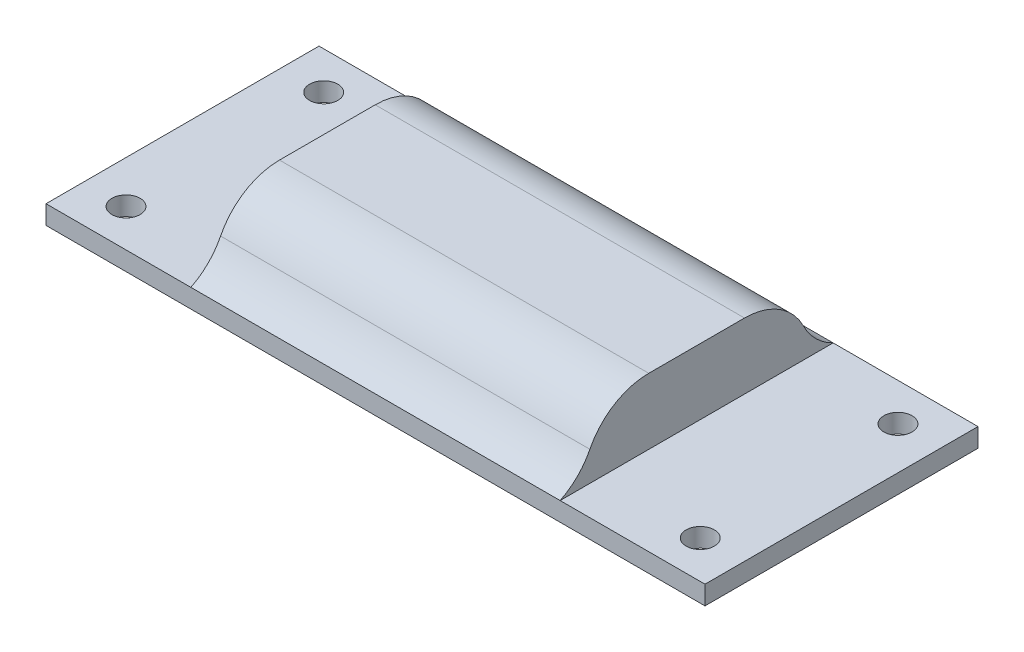
SolidWorks part; units mm, degrees
material "Rubber"
ref_plane "Front Plane" through (0, 0, 0) normal (0, 0, 1) x (1, 0, 0)
ref_plane "Top Plane" through (0, 0, 0) normal (0, 1, 0) x (1, 0, 0)
ref_plane "Right Plane" through (0, 0, 0) normal (1, 0, 0) x (0, 0, -1)
sketch "Sketch1" plane through (0, 0, 0) normal (0, 1, 0) x (1, 0, 0)
  line L1 (35, 14.5) -> (-35, 14.5)
  line L2 (35, 14.5) -> (35, -14.5)
  line L3 (35, -14.5) -> (-35, -14.5)
  line L4 (-35, 14.5) -> (-35, -14.5)
  line L5 (35, 14.5) -> (-35, -14.5) construction
  line L6 (35, -14.5) -> (-35, 14.5) construction
  circle A0 centre (-30.4996, 10.4982) radius 1.5
  circle A2 centre (30.5004, 10.4982) radius 1.5
  circle A4 centre (-30.4996, -10.5018) radius 1.5
  circle A5 centre (30.5004, -10.5018) radius 1.5
  point P0 (0, 0)
  dimension "D3" = 3
  dimension "D4" = 3
  dimension "D5" = 3
  dimension "D6" = 3
  dimension "D1" = 70
  dimension "D2" = 29
  dimension "D7" = 61
  dimension "D8" = 4.5004
  dimension "D9" = 21
  dimension "D10" = 4.0018
extrude "Boss-Extrude1" add sketch "Sketch1" along normal blind 2
sketch "Sketch3" plane through (0, 2, 0) normal (0, 1, 0) x (1, 0, 0)
  line L1 (19.6127, 10.5984) -> (-19.6127, 10.5984)
  line L2 (19.6127, 10.5984) -> (19.6127, -10.5984)
  line L3 (19.6127, -10.5984) -> (-19.6127, -10.5984)
  line L4 (-19.6127, 10.5984) -> (-19.6127, -10.5984)
  line L5 (19.6127, 10.5984) -> (-19.6127, -10.5984) construction
  line L6 (19.6127, -10.5984) -> (-19.6127, 10.5984) construction
  point P0 (0, 0)
extrude "Boss-Extrude2" add sketch "Sketch3" along normal blind 7
fillet "Fillet2" radius 7 2 edges at (0, 2, -10.5984) (0, 2, 10.5984)
fillet "Fillet3" radius 7 2 edges at (0, 9, -10.5984) (0, 9, 10.5984)
